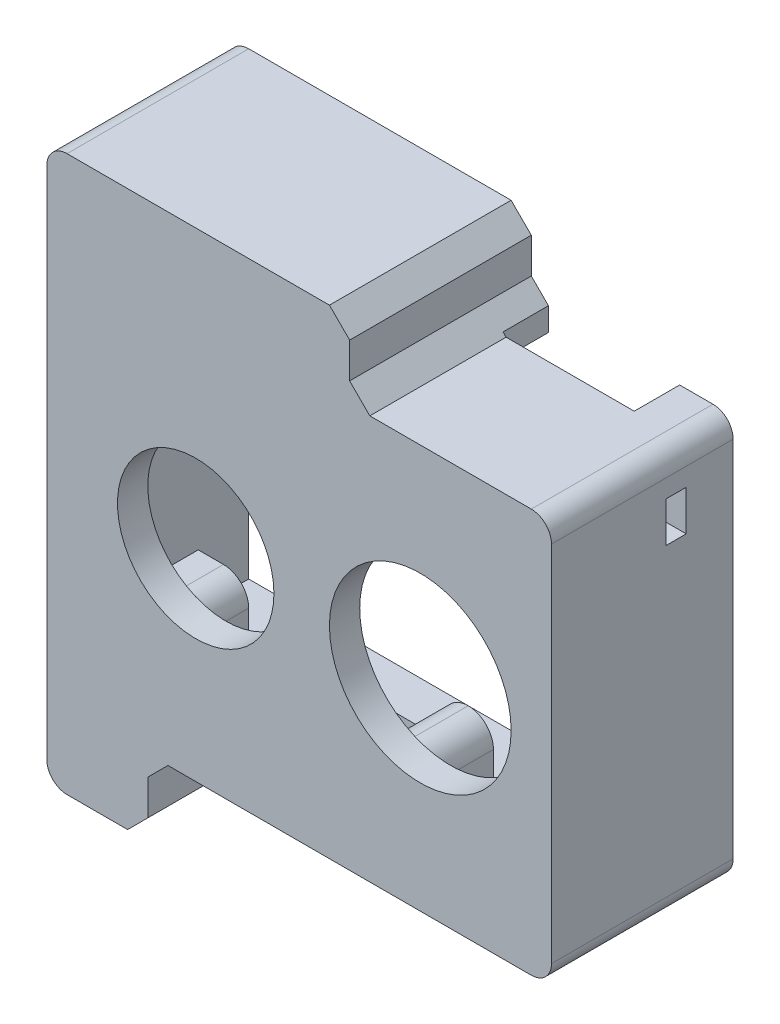
SolidWorks part; units mm, degrees
ref_plane "Front Plane" through (0, 0, 0) normal (0, 0, 1) x (1, 0, 0)
ref_plane "Top Plane" through (0, 0, 0) normal (0, 1, 0) x (1, 0, 0)
ref_plane "Right Plane" through (0, 0, 0) normal (1, 0, 0) x (0, 0, -1)
sketch "Sketch1" plane through (0, 0, 0) normal (0, 0, 1) x (1, 0, 0)
  line L0 (-15, -27.5) -> (-15, -20)
  line L1 (-25, -27.5) -> (-15, -27.5)
  line L2 (-25, -27.5) -> (-25, 27.5)
  line L3 (-25, 27.5) -> (5, 27.5)
  line L4 (25, -20) -> (25, 20)
  line L5 (0, 0) -> (25, 0) construction
  line L6 (0, 0) -> (-25, 0) construction
  line L7 (-23, -18) -> (23, -18)
  line L8 (-23, -18) -> (-23, 18)
  line L9 (-23, 18) -> (23, 18)
  line L10 (23, -18) -> (23, 18)
  line L11 (-23, -18) -> (23, 18) construction
  line L12 (-23, 18) -> (23, -18) construction
  line L13 (-15, -20) -> (25, -20)
  line L14 (5, 27.5) -> (5, 20)
  line L15 (5, 20) -> (25, 20)
  point P0 (0, 0)
  point P1 (-25, 0)
  point P4 (25, 0)
  point P6 (0, 0)
  point P18 (23, 0)
  point P20 (0, 18)
  dimension "D1" = 55
  dimension "D2" = 30
  dimension "D3" = 46
  dimension "D4" = 36
  dimension "D5" = 40
  dimension "D6" = 10
  dimension "D7" = 50
extrude "Boss-Extrude1" add sketch "Sketch1" along normal blind 15
sketch "Sketch2" plane through (0, 0, 15) normal (0, 0, 1) x (1, 0, 0)
  line L12 (-25, 27.5) -> (-25, -27.5)
  line L13 (-25, -27.5) -> (-15, -27.5)
  line L14 (-15, -27.5) -> (-15, -20)
  line L15 (-15, -20) -> (25, -20)
  line L16 (25, -20) -> (25, 20)
  line L17 (25, 20) -> (5, 20)
  line L18 (5, 20) -> (5, 27.5)
  line L19 (5, 27.5) -> (-25, 27.5)
  line L20 (-25, 27.5) -> (-25, -27.5)
  line L21 (-25, -27.5) -> (-15, -27.5)
  line L22 (-15, -27.5) -> (-15, -20)
  line L23 (-15, -20) -> (25, -20)
  line L24 (25, -20) -> (25, 20)
  line L25 (25, 20) -> (5, 20)
  line L26 (5, 20) -> (5, 27.5)
  line L27 (5, 27.5) -> (-25, 27.5)
  dimension "D1" = 0
extrude "Boss-Extrude2" add sketch "Sketch2" along normal blind 3
sketch "Sketch3" plane through (0, 0, 18) normal (0, 0, 1) x (1, 0, 0)
  circle A0 centre (-10.25, 0) radius 7.75
  circle A1 centre (12, 0) radius 9
  dimension "D1" = 18
  dimension "D2" = 15.5
  dimension "D3" = 10.25
  dimension "D4" = 12
extrude "Cut-Extrude1" cut sketch "Sketch3" against normal blind 10
sketch "Sketch4" plane through (0, 0, 15) normal (0, 0, -1) x (-1, 0, 0)
  line L0 (18, -18) -> (18, -13)
  line L1 (23, -18) -> (-23, -18) construction
  line L2 (18, -13) -> (23, -13)
  line L3 (23, 18) -> (23, -18) construction
  line L4 (23, -18) -> (23, -13)
  line L5 (23, -18) -> (18, -18)
  line L6 (-23, 18) -> (23, 18) construction
  line L7 (-1.248, -18) -> (-6.248, -18)
  line L8 (-1.248, -18) -> (-1.248, -13)
  line L9 (-1.248, -13) -> (-6.248, -13)
  line L10 (-6.248, -18) -> (-6.248, -13)
  line L11 (-1.248, 18) -> (-6.248, 18)
  line L12 (-1.248, 18) -> (-1.248, 13)
  line L13 (-1.248, 13) -> (-6.248, 13)
  line L14 (-6.248, 18) -> (-6.248, 13)
  line L16 (18, 18) -> (23, 18)
  line L17 (18, 18) -> (18, 13)
  line L18 (18, 13) -> (23, 13)
  line L19 (23, 18) -> (23, 13)
  circle A0 centre (20.252, -15.1962) radius 1
  circle A1 centre (-3.748, -15.1962) radius 1
  circle A2 centre (-3.748, 15.2038) radius 1
  circle A3 centre (20.252, 15.2038) radius 1
  point P36 (-3.748, -18)
  dimension "D1" = 2
  dimension "D2" = 5
  dimension "D4" = 24
  dimension "D5" = 30.4
extrude "Boss-Extrude3" add sketch "Sketch4" along normal blind 10
fillet "Fillet1" radius 2.5 6 edges at (6.248, -13, 10) (1.248, -13, 10) (-18, -13, 10) (-18, 13, 10) (1.248, 13, 10) (6.248, 13, 10)
sketch "Sketch6" plane through (0, 0, -3) normal (0, 0, -1) x (-1, 0, 0)
  line L0 (20, 22.5) -> (20, -22.5) construction
  circle A0 centre (0, 22.5) radius 1
  circle A1 centre (20, 22.5) radius 1
  circle A2 centre (20, -22.5) radius 1
  dimension "D3" = 2
  dimension "D1" = 22.5
  dimension "D2" = 20
  dimension "D4" = 45
extrude "Cut-Extrude2" cut sketch "Sketch6" against normal blind 10
chamfer "Chamfer1" distance 2 angle 45 4 edges at (-15, -27.5, 9) (5, 27.5, 9) (-15, -20, 9) (5, 20, 9)
fillet "Fillet2" radius 2 4 edges at (-25, 27.5, 9) (-25, -27.5, 9) (25, 20, 9) (25, -20, 9)
sketch "Sketch7" plane through (0, 18, 0) normal (0, -1, 0) x (1, 0, 0)
  line L0 (23, 0) -> (-23, 0) construction
  line L1 (6.7, 0) -> (19.7, 0)
  line L2 (6.7, 0) -> (6.7, 4.5)
  line L3 (6.7, 4.5) -> (19.7, 4.5)
  line L4 (19.7, 0) -> (19.7, 4.5)
  point P6 (13.2, 0)
  dimension "D1" = 13
  dimension "D2" = 4.5
  dimension "D3" = 13.2
extrude "Cut-Extrude3" cut sketch "Sketch7" against normal blind 10
sketch "Sketch8" plane through (0, -18, 0) normal (0, 1, 0) x (1, 0, 0)
  line L0 (-23, 0) -> (23, 0) construction
  line L1 (22.2, 0) -> (9.2, 0)
  line L2 (22.2, 0) -> (22.2, -9.5)
  line L3 (22.2, -9.5) -> (11.7, -9.5)
  line L4 (9.2, 0) -> (9.2, -4.5)
  line L5 (11.7, -9.5) -> (11.7, -4.5)
  line L6 (11.7, -4.5) -> (9.2, -4.5)
  line L8 (0.7, -4.2) -> (-8.3, -4.2)
  line L9 (0.7, -4.2) -> (0.7, -8.2)
  line L10 (0.7, -8.2) -> (-8.3, -8.2)
  line L11 (-8.3, -4.2) -> (-8.3, -8.2)
  point P6 (15.7, 0)
  point P14 (-3.8, -4.2)
  dimension "D1" = 13
  dimension "D2" = 15.7
  dimension "D3" = 9.5
  dimension "D4" = 10.5
  dimension "D5" = 4.5
  dimension "D6" = 3.8
  dimension "D7" = 9
  dimension "D8" = 4.2
  dimension "D9" = 4
extrude "Cut-Extrude4" cut sketch "Sketch8" against normal blind 10
sketch "Sketch9" plane through (23, 0, 0) normal (-1, 0, 0) x (0, 0, 1)
  line L1 (4.65, 12.2) -> (6.65, 12.2)
  line L2 (4.65, 12.2) -> (4.65, 16.2)
  line L3 (4.65, 16.2) -> (6.65, 16.2)
  line L4 (6.65, 12.2) -> (6.65, 16.2)
  point P4 (4.65, 14.2)
  dimension "D1" = 2
  dimension "D2" = 4.65
  dimension "D3" = 14.2
  dimension "D4" = 4
extrude "Cut-Extrude5" cut sketch "Sketch9" against normal blind 10
